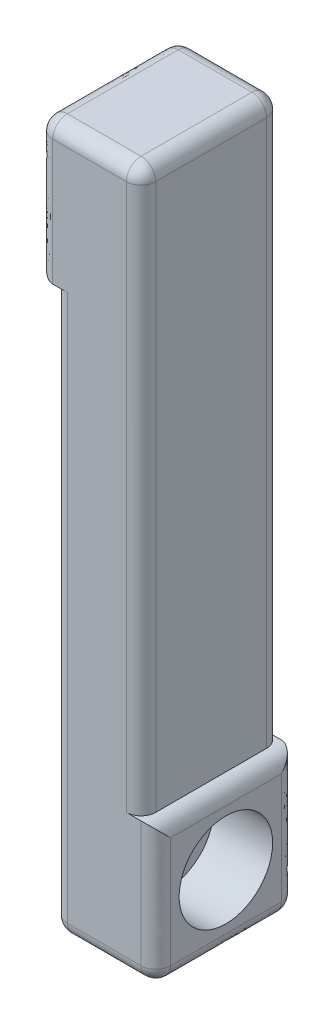
SolidWorks part; units mm, degrees
ref_plane "Front Plane" through (0, 0, 0) normal (0, 0, 1) x (1, 0, 0)
ref_plane "Top Plane" through (0, 0, 0) normal (0, 1, 0) x (1, 0, 0)
ref_plane "Right Plane" through (0, 0, 0) normal (1, 0, 0) x (0, 0, -1)
sketch "Sketch2" plane through (0, 0, 0) normal (1, 0, 0) x (0, 0, -1)
  line L1 (-4.7625, 23.8125) -> (4.7625, 23.8125)
  line L2 (-4.7625, 23.8125) -> (-4.7625, -23.8125)
  line L3 (-4.7625, -23.8125) -> (4.7625, -23.8125)
  line L4 (4.7625, 23.8125) -> (4.7625, -23.8125)
  line L5 (-4.7625, 23.8125) -> (4.7625, -23.8125) construction
  line L6 (-4.7625, -23.8125) -> (4.7625, 23.8125) construction
  point P0 (0, 0)
  dimension "D1" = 47.625
  dimension "D2" = 9.525
extrude "Boss-Extrude1" add sketch "Sketch2" along normal mid plane 6
ref_plane "Plane1" through (-3, 0, 0) normal (-1, 0, 0) x (0, 0, 1)
ref_plane "Plane2" through (3, 0, 0) normal (1, 0, 0) x (0, 0, -1)
sketch "Sketch5" plane through (-3, 0, 0) normal (-1, 0, 0) x (0, 0, 1)
  line L0 (4.7625, 23.8125) -> (4.7625, -23.8125) construction
  line L1 (-4.7625, 23.8125) -> (4.7625, 23.8125)
  line L2 (-4.7625, 23.8125) -> (-4.7625, 14.2875)
  line L3 (-4.7625, 14.2875) -> (4.7625, 14.2875)
  line L4 (4.7625, 23.8125) -> (4.7625, 14.2875)
  line L5 (-4.7625, 23.8125) -> (4.7625, 14.2875) construction
  line L6 (-4.7625, 14.2875) -> (4.7625, 23.8125) construction
  line L7 (-4.7625, 23.8125) -> (4.7625, 23.8125) construction
  point P0 (0, 19.05)
extrude "Boss-Extrude2" add sketch "Sketch5" along normal blind 1
sketch "Sketch7" plane through (3, 0, 0) normal (1, 0, 0) x (0, 0, -1)
  line L0 (4.7625, -23.8125) -> (4.7625, 23.8125) construction
  line L1 (-4.7625, -23.8125) -> (4.7625, -23.8125)
  line L2 (-4.7625, -23.8125) -> (-4.7625, -14.2875)
  line L3 (-4.7625, -14.2875) -> (4.7625, -14.2875)
  line L4 (4.7625, -23.8125) -> (4.7625, -14.2875)
  line L5 (-4.7625, -23.8125) -> (4.7625, -14.2875) construction
  line L6 (-4.7625, -14.2875) -> (4.7625, -23.8125) construction
  line L7 (-4.7625, -23.8125) -> (4.7625, -23.8125) construction
  point P0 (0, -19.05)
  dimension "D1" = 4.7625
extrude "Boss-Extrude3" add sketch "Sketch7" along normal blind 1
sketch "Sketch8" plane through (4, 0, 0) normal (1, 0, 0) x (0, 0, -1)
  line L0 (-4.7625, -23.8125) -> (4.7625, -23.8125) construction
  circle A0 centre (0, -19.05) radius 3.175
  dimension "D1" = 4.7625
extrude "Cut-Extrude2" cut sketch "Sketch8" against normal blind 4
sketch "Sketch9" plane through (-4, 0, 0) normal (-1, 0, 0) x (0, 0, 1)
  line L0 (4.7625, 23.8125) -> (-4.7625, 23.8125) construction
  circle A0 centre (0, 19.05) radius 3.175
  dimension "D1" = 4.7625
extrude "Cut-Extrude3" cut sketch "Sketch9" against normal blind 4
fillet "Fillet6" radius 1 14 edges at (4, -19.05, -4.7625) (4, -19.05, 4.7625) (-4, 19.05, 4.7625) (-4, 19.05, -4.7625) (0.5, -23.8125, -4.7625) (-3, -23.8125, 0) (0.5, -23.8125, 4.7625) (4, -23.8125, 0) (4, -14.2875, 0) (-4, 14.2875, 0) (-4, 23.8125, 0) (-0.5, 23.8125, 4.7625) (3, 23.8125, 0) (-0.5, 23.8125, -4.7625) first distance on face at (0, 0, -4.7625) first distance on face at (0, 0, 4.7625) first distance on face at (-3, -4.7625, 0) first distance on face at (0.5, -23.8125, 0) first distance on face at (3.5, -14.2875, 0) first distance on face at (-3.5, 14.2875, 0) first distance on face at (-4, 19.05, 3.175) first distance on face at (3, 4.7625, 0)
fillet "Fillet7" radius 1 8 edges at (-2.8712, -23.3035, -4.6337) (-3, -4.2625, -4.7625) (2.8712, 23.3035, -4.6337) (3, 4.2625, -4.7625) (2.8712, 23.3035, 4.6337) (3, 4.2625, 4.7625) (-2.8712, -23.3035, 4.6337) (-3, -4.2625, 4.7625) first distance on face at (-2.6856, -23.308, -0.25) first distance on face at (-3, -4.2625, -1.1906) first distance on face at (-0.2822, 23.4352, -4.2303) first distance on face at (3, 4.2625, -1.1906) first distance on face at (2.6856, 23.308, -0.25) first distance on face at (0.0322, -23.1852, 4.4803)
